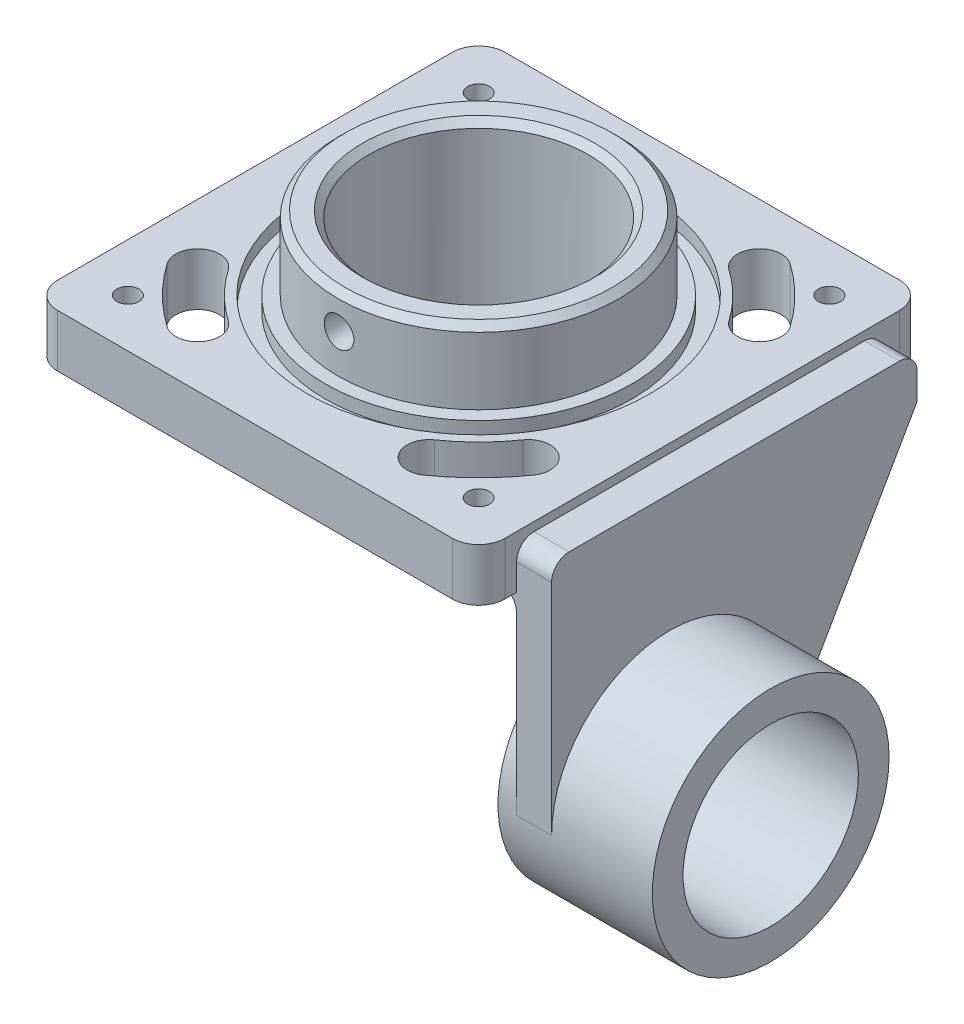
SolidWorks part; units mm, degrees
ref_plane "Face" through (0, 0, 0) normal (0, 0, 1) x (1, 0, 0)
ref_plane "Dessus" through (0, 0, 0) normal (0, 1, 0) x (1, 0, 0)
ref_plane "Droite" through (0, 0, 0) normal (1, 0, 0) x (0, 0, -1)
sketch "Esquisse1" plane through (0, 0, 0) normal (0, 1, 0) x (1, 0, 0)
  line L0 (-59.8186, 41.8854) -> (0, 0) construction
  line L1 (-80.9625, -80.9625) -> (80.9625, -80.9625)
  line L2 (-80.9625, -80.9625) -> (-80.9625, 80.9625)
  line L3 (-80.9625, 80.9625) -> (80.9625, 80.9625)
  line L4 (80.9625, -80.9625) -> (80.9625, 80.9625)
  line L5 (-80.9625, -80.9625) -> (80.9625, 80.9625) construction
  line L6 (-80.9625, 80.9625) -> (80.9625, -80.9625) construction
  line L7 (0, 0) -> (-41.8854, 59.8186) construction
  circle A0 centre (0, 0) radius 39.6875
  arc A1 (-41.8854, 59.8186) -> (-59.8186, 41.8854) centre (0, 0) ccw construction
  arc A2 (-46.4382, 66.3206) -> (-66.3206, 46.4382) centre (0, 0) ccw
  arc A3 (-37.3327, 53.3166) -> (-53.3166, 37.3327) centre (0, 0) ccw
  arc A4 (-37.3327, 53.3166) -> (-46.4382, 66.3206) centre (-41.8854, 59.8186) ccw
  arc A5 (-66.3206, 46.4382) -> (-53.3166, 37.3327) centre (-59.8186, 41.8854) ccw
  arc A6 (59.8186, 41.8854) -> (41.8854, 59.8186) centre (0, 0) ccw construction
  arc A7 (66.3206, 46.4382) -> (46.4382, 66.3206) centre (0, 0) ccw
  arc A8 (53.3166, 37.3327) -> (37.3327, 53.3166) centre (0, 0) ccw
  arc A9 (53.3166, 37.3327) -> (66.3206, 46.4382) centre (59.8186, 41.8854) ccw
  arc A10 (46.4382, 66.3206) -> (37.3327, 53.3166) centre (41.8854, 59.8186) ccw
  arc A11 (41.8854, -59.8186) -> (59.8186, -41.8854) centre (0, 0) ccw construction
  arc A12 (46.4382, -66.3206) -> (66.3206, -46.4382) centre (0, 0) ccw
  arc A13 (37.3327, -53.3166) -> (53.3166, -37.3327) centre (0, 0) ccw
  arc A14 (37.3327, -53.3166) -> (46.4382, -66.3206) centre (41.8854, -59.8186) ccw
  arc A15 (66.3206, -46.4382) -> (53.3166, -37.3327) centre (59.8186, -41.8854) ccw
  arc A16 (-59.8186, -41.8854) -> (-41.8854, -59.8186) centre (0, 0) ccw construction
  arc A17 (-66.3206, -46.4382) -> (-46.4382, -66.3206) centre (0, 0) ccw
  arc A18 (-53.3166, -37.3327) -> (-37.3327, -53.3166) centre (0, 0) ccw
  arc A19 (-53.3166, -37.3327) -> (-66.3206, -46.4382) centre (-59.8186, -41.8854) ccw
  arc A20 (-46.4382, -66.3206) -> (-37.3327, -53.3166) centre (-41.8854, -59.8186) ccw
  point P0 (0, 0)
  point P10 (-51.6365, 51.6365)
  point P23 (51.6365, 51.6365)
  point P30 (51.6365, -51.6365)
  point P37 (-51.6365, -51.6365)
  point P42 (0, 0)
  dimension "D3" = 79.375
  dimension "D6" = 7.9375
  dimension "D1" = 161.925
  dimension "D2" = 161.925
  dimension "D4" = 73.025
  dimension "D5" = 20
  dimension "D7" = 4
extrude "Boss.-Extru.1" add sketch "Esquisse1" against normal blind 19.05
hole_wizard "Trou taraudé 3/8-161" positions "Esquisse2" profile "Esquisse3" tap size "3/8-16" standard "Ansi Inch" end condition through all
sketch "Esquisse2" plane through (0, 0, 0) normal (0, 1, 0) x (1, 0, 0)
  line L0 (80.9625, 80.9625) -> (-80.9625, 80.9625) construction
  line L1 (-80.9625, 80.9625) -> (-80.9625, -80.9625) construction
  point P0 (-63.5, 63.5)
  point P2 (63.5, 63.5)
  point P5 (-63.5, -63.5)
  point P7 (63.5, -63.5)
  dimension "D1" = 127
  dimension "D2" = 127
  dimension "D3" = 17.4625
  dimension "D4" = 17.4625
sketch "Esquisse3" plane through (-63.5, 0, -63.5) normal (1, 0, 0) x (0, 0, 1)
  line L0 (0, 0) -> (0, 19.05)
  line L1 (0, 19.05) -> (3.9687, 19.05)
  line L2 (3.9687, 19.05) -> (3.9687, 0)
  line L5 (3.9687, 0) -> (0, 0)
  line L11 (0, -6.35) -> (0, 107.95) construction
  dimension "Diamètre du trou pour taraudage jusqu'au prochain" = 7.9375
  dimension "Profondeur du trou pour taraudage jusqu'au prochain" = 19.05
cosmetic thread "Filetage de perçage1" parameters "D2"=9.525
cosmetic thread "Filetage de perçage2" parameters "D2"=9.525
cosmetic thread "Filetage de perçage3" parameters "D2"=9.525
cosmetic thread "Filetage de perçage4" parameters "D2"=9.525
sketch "Esquisse4" plane through (0, 0, 0) normal (0, 1, 0) x (1, 0, 0)
  circle A0 centre (0, 0) radius 55.5625
  circle A1 centre (0, 0) radius 61.9125
  dimension "D1" = 111.125
  dimension "D2" = 123.825
extrude "Enlèv. mat.-Extru.1" cut sketch "Esquisse4" against normal blind 4.7625 contours A1 | A0
sketch "Esquisse5" plane through (0, 0, 0) normal (0, 1, 0) x (1, 0, 0)
  circle A0 centre (0, 0) radius 50.8
  circle A1 centre (0, 0) radius 39.6875
  dimension "D1" = 101.6
  dimension "D2" = 79.375
extrude "Boss.-Extru.2" add sketch "Esquisse5" along normal blind 26.67
chamfer "Chanfrein1" [suppressed] distance 2.3813 angle 45
fillet "Congé1" radius 9.525 4 edges at (-80.9625, -9.525, -80.9625) (80.9625, -9.525, -80.9625) (-80.9625, -9.525, 80.9625) (80.9625, -9.525, 80.9625)
ref_plane "Plan1" through (0, 0, 50.8) normal (0, 0, 1) x (1, 0, 0)
hole_wizard "Trou taraudé 1/2-131" positions "Esquisse9" profile "Esquisse10" tap size "1/2-13" standard "Ansi Inch" end condition up to next
sketch "Esquisse9" plane through (0, 0, 50.8) normal (0, 0, 1) x (1, 0, 0)
  line L0 (50.8, 26.67) -> (-50.8, 26.67) construction
  point P0 (0, 13.97)
  point P5 (0, 0)
  dimension "D1" = 12.7
sketch "Esquisse10" plane through (0, 13.97, 50.8) normal (1, 0, 0) x (0, -1, 0)
  line L0 (0, 0) -> (0, 11.1125)
  line L1 (0, 11.1125) -> (5.3581, 11.1125)
  line L2 (5.3581, 11.1125) -> (5.3581, 0)
  line L5 (5.3581, 0) -> (0, 0)
  line L11 (0, -6.35) -> (0, 107.95) construction
  dimension "Diamètre du trou pour taraudage jusqu'au prochain" = 10.7163
  dimension "Profondeur du trou pour taraudage jusqu'au prochain" = 11.1125
cosmetic thread "Filetage de perçage5" parameters "D2"=12.7
chamfer "Chanfrein2" distance 2.3813 angle 45 2 edges at (0, 26.67, 39.6875) (0, 26.67, 50.8)
sketch "Esquisse11" plane through (0, -19.05, 0) normal (0, -1, 0) x (-1, 0, 0)
  circle A0 centre (0, 0) radius 53.975
  circle A2 centre (0, 0) radius 39.6875
  dimension "D1" = 107.95
  dimension "D2" = 79.375
extrude "Boss.-Extru.3" add sketch "Esquisse11" along normal blind 19.05
chamfer "Chanfrein4" distance 2.3813 angle 45 1 edges at (0, -38.1, -39.6875)
sketch "Esquisse13" plane through (80.9625, 0, 0) normal (1, 0, 0) x (0, 0, -1)
  line L0 (-53.975, -38.1) -> (53.975, -38.1) construction
  line L1 (-67.2465, -88.9) -> (-67.2465, -3.175)
  line L2 (-67.2465, -3.175) -> (65.0875, -3.175)
  line L3 (65.0875, -3.175) -> (65.0875, -19.05)
  line L4 (65.0875, -19.05) -> (12.7976, -110.2242)
  line L5 (-71.4375, 0) -> (71.4375, 0) construction
  line L6 (80.9625, 0) -> (80.9625, -19.05) construction
  line L7 (-71.4375, -19.05) -> (71.4375, -19.05) construction
  arc A0 (-67.2465, -88.9) -> (12.7976, -110.2242) centre (-24.384, -88.9) ccw
  circle A1 centre (-24.384, -88.9) radius 31.75
  point P15 (13.5436, -108.8672)
  point P16 (65.0875, -11.0178)
  point P17 (65.0875, -19.05)
  dimension "D1" = 85.725
  dimension "D2" = 63.5
  dimension "D3" = 24.384
  dimension "D4" = 50.8
  dimension "D5" = 3.175
  dimension "D6" = 15.875
extrude "Boss.-Extru.4" add sketch "Esquisse13" along normal blind 12.7
fillet "Congé2" radius 6.35 2 edges at (87.3125, -3.175, -65.0875) (87.3125, -3.175, 67.2465)
sketch "Esquisse15" plane through (93.6625, 0, 0) normal (1, 0, 0) x (0, 0, -1)
  line L0 (-24.384, -57.15) -> (-24.384, -120.65) construction
  line L1 (-56.134, -88.9) -> (7.366, -88.9) construction
  circle A0 centre (-24.384, -88.9) radius 31.75 construction
  circle A1 centre (-24.384, -88.9) radius 42.8625
  circle A2 centre (-24.384, -88.9) radius 31.75
  dimension "D1" = 85.725
fillet "Congé3" radius 6.35 1 edges at (80.9625, -19.05, 1.0795)
ref_plane "Plan2" through (74.2442, 0, 0) normal (1, 0, 0) x (0, 0, -1)
sketch "Esquisse18" plane through (80.9625, 0, 0) normal (-1, 0, 0) x (0, 0, 1)
  circle A0 centre (24.384, -88.9) radius 42.8625
  circle A1 centre (24.384, -88.9) radius 31.75
  dimension "D1" = 85.725
  dimension "D2" = 63.5
extrude "Boss.-Extru.6" add sketch "Esquisse18" along normal up to surface (6.7183 mm away) up to plane "Plan2"
sketch "Esquisse19" plane through (93.6625, 0, 0) normal (1, 0, 0) x (0, 0, -1)
  line L0 (-24.384, -57.15) -> (-24.384, -120.65) construction
  line L1 (-56.134, -88.9) -> (7.366, -88.9) construction
  circle A1 centre (-24.384, -88.9) radius 31.75 construction
  circle A2 centre (-24.384, -88.9) radius 42.8625
  circle A3 centre (-24.384, -88.9) radius 31.75
  dimension "D1" = 85.725
  dimension "D2" = 63.5
extrude "Boss.-Extru.7" add sketch "Esquisse19" along normal blind 36.4617
